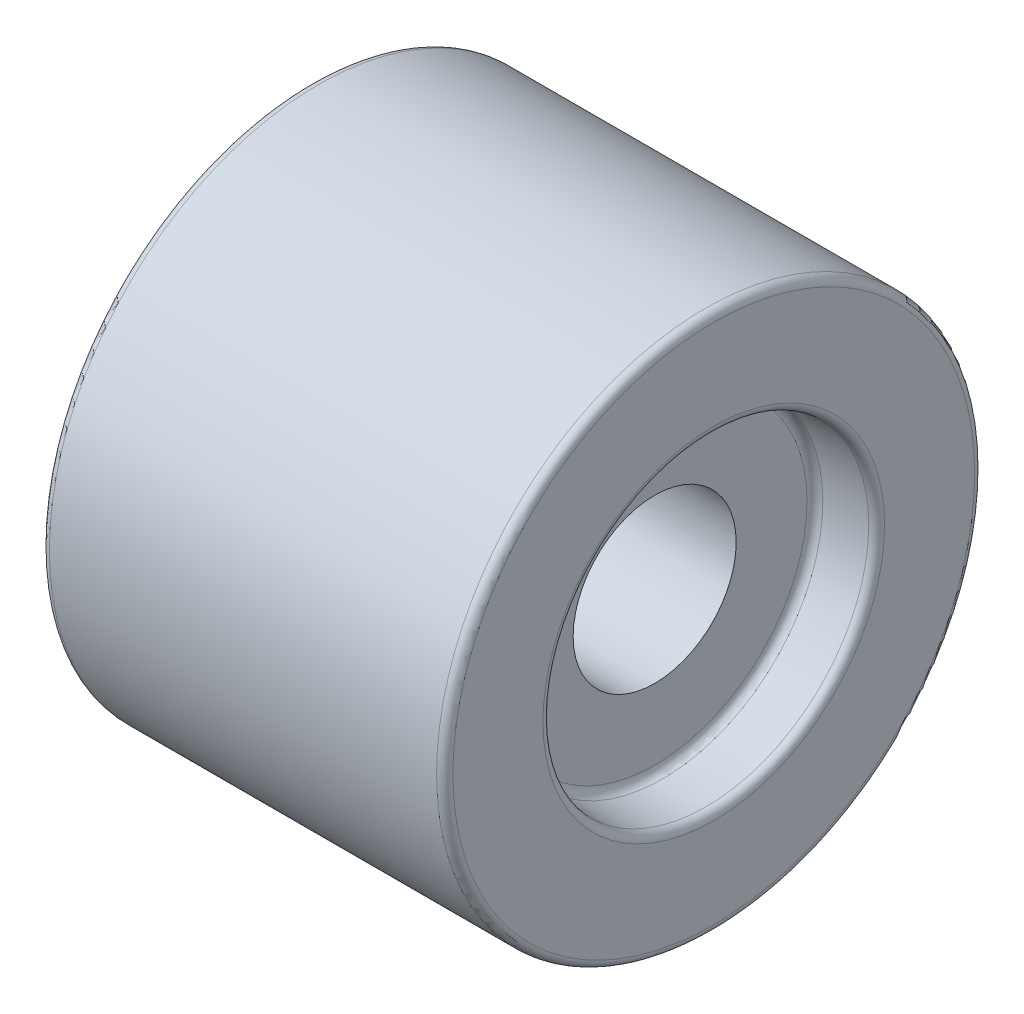
SolidWorks part; units mm, degrees
ref_plane "前视基准面" through (0, 0, 0) normal (0, 0, 1) x (1, 0, 0)
ref_plane "上视基准面" through (0, 0, 0) normal (0, 1, 0) x (1, 0, 0)
ref_plane "右视基准面" through (0, 0, 0) normal (1, 0, 0) x (0, 0, -1)
sketch "草图1" plane through (0, 0, 0) normal (0, 0, 1) x (1, 0, 0)
  line L0 (-49.5, 0) -> (49.5, 0)
  line L1 (-49.5, 66) -> (49.5, 66)
  line L2 (-49.5, 66) -> (-49.5, 0)
  line L4 (49.5, 66) -> (49.5, 0)
  line L5 (-49.5, 66) -> (0, 0) construction
  line L6 (0, 0) -> (49.5, 66) construction
  point P0 (0, 0)
revolve "旋转2" add sketch "草图1" angle 360 about L0
ref_plane "基准面1" through (0, 0, 0) normal (1, 0, 0) x (0, 0, -1)
sketch "草图2" plane through (-49.5, 0, 0) normal (-1, 0, 0) x (0, 0, 1)
  circle A0 centre (0, 0) radius 40
extrude "切除-拉伸1" cut sketch "草图2" against normal blind 14.5 draft 2.9
mirror "镜向1" about plane through (0, 0, 0) normal (1, 0, 0) of "切除-拉伸1"
fillet "圆角1" radius 2 5 edges at (-49.5, 0, 66) (35, 0, -39.2655) (49.5, 0, 40) (49.5, 0, 66) (-35, 0, 39.2655)
sketch "草图3" plane through (-35, 0, 0) normal (-1, 0, 0) x (0, 0, 1)
  circle A0 centre (0, 0) radius 20
extrude "切除-拉伸2" cut sketch "草图3" against normal blind 100
